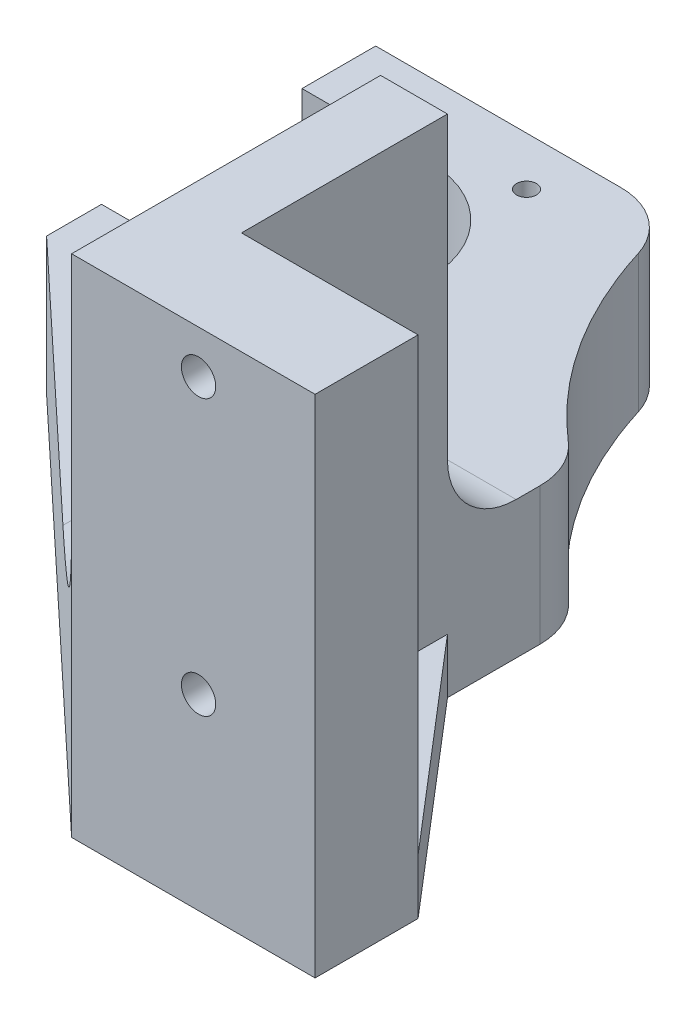
SolidWorks part; units mm, degrees
ref_plane "Front Plane" through (0, 0, 0) normal (0, 0, 1) x (1, 0, 0)
ref_plane "Top Plane" through (0, 0, 0) normal (0, 1, 0) x (1, 0, 0)
ref_plane "Right Plane" through (0, 0, 0) normal (1, 0, 0) x (0, 0, -1)
sketch "Sketch1" plane through (0, 0, 0) normal (0, 0, 1) x (1, 0, 0)
  line L0 (-116, 95) -> (-116, -95) construction
  line L1 (-126, -29.3724) -> (-90.54, -29.3724)
  line L2 (-126, -29.3724) -> (-126, -103)
  line L3 (-126, -103) -> (-90.54, -103)
  line L4 (-90.54, -29.3724) -> (-90.54, -103)
  line L5 (-116, -95) -> (116, -95) construction
  dimension "D1" = 10
  dimension "D2" = 8
extrude "Boss-Extrude1" add sketch "Sketch1" along normal blind 15
sketch "Sketch2" plane through (0, 0, 0) normal (0, 0, -1) x (-1, 0, 0)
  line L0 (126, -103) -> (90.54, -103) construction
  line L1 (126, -29.3724) -> (116.2579, -29.3724)
  line L2 (126, -29.3724) -> (126, -103)
  line L3 (126, -103) -> (116.2579, -103)
  line L4 (116.2579, -29.3724) -> (116.2579, -103)
extrude "Boss-Extrude2" add sketch "Sketch2" along normal up to surface (30 mm away)
sketch "Sketch3" plane through (0, -103, 0) normal (0, -1, 0) x (1, 0, 0)
  line L0 (-116.2579, -30) -> (-90.54, 0)
  line L1 (-90.54, 0) -> (-116.2579, 0)
  line L2 (-116.2579, 0) -> (-116.2579, -30)
extrude "Boss-Extrude3" add sketch "Sketch3" against normal up to surface (8 mm away)
hole_wizard "Tap Drill for M6 Tap2" positions "3DSketch4" profile "Sketch8" hole size "M6" standard "ISO" end condition through all
sketch3d "3DSketch4"
  point P0 (-107.5093, -35.6384, 15)
  point P2 (-107.5093, -75.7054, 15)
sketch "Sketch8" plane through (-107.5093, -35.6384, 15) normal (1, 0, 0) x (0, -1, 0)
  line L0 (0, 0) -> (0, 45)
  line L1 (0, 45) -> (2.5, 45)
  line L2 (2.5, 45) -> (2.5, 0)
  line L5 (2.5, 0) -> (0, 0)
  line L11 (0, -6.35) -> (0, 107.95) construction
  dimension "Thru Hole Dia." = 5
  dimension "Thru Hole Depth" = 45
sketch "Sketch9" plane through (0, -29.3724, 0) normal (0, 1, 0) x (1, 0, 0)
  line L0 (-126, -15) -> (-182.3588, 41.8776)
  line L1 (-182.3588, 41.8776) -> (-182.3588, 54.4776)
  line L2 (-182.3588, 54.4776) -> (-177.6569, 54.4776)
  line L3 (-116.2579, 30) -> (-116.2579, 41.8776)
  line L4 (-116.2579, 41.8776) -> (-159.1803, 85.1951)
  line L5 (-159.1803, 85.1951) -> (-160.6033, 86.9776)
  line L6 (-160.6033, 86.9776) -> (-182.3588, 87.0776)
  line L7 (-182.3588, 87.0776) -> (-182.3588, 74.4785)
  line L8 (-182.3588, 74.4785) -> (-177.6569, 74.4785)
  line L9 (-177.6569, 74.4785) -> (-164.2586, 74.4785)
  line L10 (-177.6569, 54.4776) -> (-164.2586, 54.4776)
  line L11 (-126, -15) -> (-90.54, -15)
  line L12 (-126, -15) -> (-126, 30)
  line L13 (-126, -15) -> (-126, 30) construction
  line L14 (-126, 30) -> (-116.2579, 30)
  line L17 (-90.54, 0) -> (-116.2579, 0)
  line L18 (-116.2579, 0) -> (-116.2579, 30)
  line L19 (-116.2579, 30) -> (-126, 30)
  line L20 (-126, 30) -> (-126, -15)
  line L21 (-126, -15) -> (-90.54, -15)
  line L22 (-90.54, -15) -> (-90.54, 0)
  line L27 (-126, -15) -> (-90.54, -15)
  arc A0 (-164.2586, 74.4785) -> (-164.2586, 54.4776) centre (-164.2586, 64.478) cw
  dimension "D1" = 0
sketch "Sketch10" plane through (0, -29.3724, 0) normal (0, 1, 0) x (1, 0, 0)
  line L0 (-126, -15) -> (-183.6888, 39.0426)
  line L8 (-116.2579, 48.2589) -> (-116.2579, 30)
  line L9 (-116.2579, 30) -> (-126, 30)
  line L10 (-126, 30) -> (-126, -15)
  line L32 (-183.6888, 39.0426) -> (-183.6887, 47.0423)
  line L33 (-155.286, 86.9776) -> (-140.248, 86.9776)
  line L38 (-165.1385, 47.0423) -> (-183.6887, 47.0423)
  line L40 (-183.6882, 76.2423) -> (-183.6882, 86.9776)
  line L41 (-183.6882, 86.9776) -> (-155.286, 86.9776)
  line L42 (-183.6882, 76.2423) -> (-165.1385, 76.2423)
  arc A8 (-165.1385, 47.0423) -> (-165.1385, 76.2423) centre (-165.1385, 61.6423) ccw
  spline S0 degree 2 poles (-140.248, 86.9776) (-135.0409, 62.4382) (-116.2579, 48.2589) knots 0 0 0 1 1 1
extrude "Boss-Extrude4" add sketch "Sketch10" along normal blind 20 from surface starting at face at (-109.8676, -103, -6)
fillet "Fillet2" radius 10 1 edges at (-121.129, -83, -30)
fillet "Fillet3" radius 10 1 edges at (-140.248, -93, -86.9776)
fillet "Fillet4" radius 10 1 edges at (-116.2579, -93, -48.2589)
fillet "Fillet6" radius 20 1 edges at (-126, -83, -12.5)
sketch "Sketch15" plane through (0, -103, 0) normal (0, -1, 0) x (1, 0, 0)
  circle A1 centre (-154.6387, -43.3922) radius 1.65
  circle A2 centre (-175.6382, -79.8925) radius 1.6741
  circle A3 centre (-154.6382, -79.8922) radius 1.65
  circle A4 centre (-175.6387, -43.3925) radius 1.65
hole_wizard "M2.5 Clearance Hole4" positions "Sketch20" profile "Sketch21" hole size "M2.5" standard "ISO" end condition through all
sketch "Sketch20" plane through (0, -103, 0) normal (0, -1, 0) x (-1, 0, 0)
  point P0 (175.6382, 79.8925)
  point P3 (154.6382, 79.8922)
  point P6 (154.6387, 43.3922)
  point P9 (175.6387, 43.3925)
sketch "Sketch21" plane through (-175.6382, -103, -79.8925) normal (1, 0, 0) x (0, 0, -1)
  line L0 (0, 0) -> (0, 73.6276)
  line L1 (0, 73.6276) -> (1.45, 73.6276)
  line L2 (1.45, 73.6276) -> (1.45, 0)
  line L5 (1.45, 0) -> (0, 0)
  line L11 (0, -6.35) -> (0, 107.95) construction
  dimension "Thru Hole Dia." = 2.9
  dimension "Thru Hole Depth" = 73.6276
